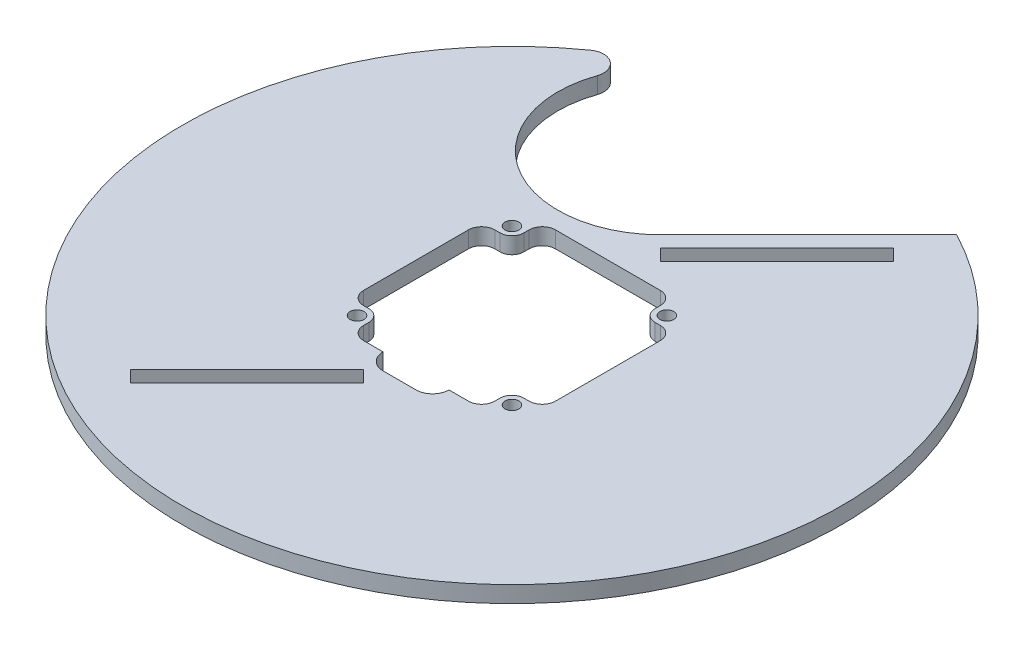
SolidWorks part; units mm, degrees
ref_plane "前基準面" through (0, 0, 0) normal (0, 0, 1) x (1, 0, 0)
ref_plane "上基準面" through (0, 0, 0) normal (0, 1, 0) x (1, 0, 0)
ref_plane "右基準面" through (0, 0, 0) normal (1, 0, 0) x (0, 0, -1)
sketch "草圖1" plane through (0, 0, 0) normal (0, 1, 0) x (1, 0, 0)
  line L2 (-99.6974, -7.7735) -> (17.2836, 109.2075) construction
  line L3 (8.3612, 36.6455) -> (43.7166, 72.0009)
  line L4 (-28.5, 28.5) -> (28.5, 28.5) construction
  line L5 (-28.5, 28.5) -> (-28.5, -28.5) construction
  line L6 (-28.5, -28.5) -> (28.5, -28.5) construction
  line L7 (28.5, 28.5) -> (28.5, -28.5) construction
  line L8 (8.3612, 36.6455) -> (4.8257, 40.181)
  line L9 (-18.8989, 23.5) -> (-18.8989, 25.1) construction
  line L10 (-25.1, 18.8989) -> (-23.5, 18.8989) construction
  line L11 (-18.8989, 23.5) -> (-18.8989, 25.1) construction
  line L12 (-25.1, 18.8989) -> (-23.5, 18.8989) construction
  line L13 (23.5, 18.8989) -> (25.1, 18.8989) construction
  line L14 (18.8989, 25.1) -> (18.8989, 23.5) construction
  line L15 (18.8989, -23.5) -> (18.8989, -25.1) construction
  line L16 (25.1, -18.8989) -> (23.5, -18.8989) construction
  line L17 (-23.5, -18.8989) -> (-25.1, -18.8989) construction
  line L18 (-18.8989, -25.1) -> (-18.8989, -23.5) construction
  line L19 (-15.8989, 28.1) -> (15.8989, 28.1) construction
  line L20 (28.1, 15.8989) -> (28.1, -15.8989) construction
  line L21 (-15.8989, -28.1) -> (15.8989, -28.1) construction
  line L22 (-28.1, 15.8989) -> (-28.1, -15.8989) construction
  line L23 (-19.8989, 23.5) -> (-19.8989, 25.1)
  line L24 (-15.8989, 29.1) -> (15.8989, 29.1)
  line L25 (19.8989, 25.1) -> (19.8989, 23.5)
  line L26 (23.5, 19.8989) -> (25.1, 19.8989)
  line L27 (29.1, 15.8989) -> (29.1, -15.8989)
  line L28 (25.1, -19.8989) -> (23.5, -19.8989)
  line L29 (19.8989, -23.5) -> (19.8989, -25.1)
  line L30 (-15.8989, -29.1) -> (15.8989, -29.1)
  line L31 (-19.8989, -25.1) -> (-19.8989, -23.5)
  line L32 (-23.5, -19.8989) -> (-25.1, -19.8989)
  line L33 (-29.1, 15.8989) -> (-29.1, -15.8989)
  line L34 (-25.1, 19.8989) -> (-23.5, 19.8989)
  line L35 (43.7166, 72.0009) -> (40.181, 75.5364)
  line L36 (40.181, 75.5364) -> (4.8257, 40.181)
  line L37 (40.181, 75.5364) -> (50.7877, 86.143) construction
  line L38 (-43.7166, -72.0009) -> (-40.181, -75.5364)
  line L39 (1.2902, 43.7166) -> (46.2405, 88.6669)
  line L40 (-8.3612, -36.6455) -> (-43.7166, -72.0009)
  line L41 (-40.181, -75.5364) -> (-4.8257, -40.181)
  line L42 (-8.3612, -36.6455) -> (-4.8257, -40.181)
  arc A20 (-57.6766, 81.6909) -> (46.2405, 88.6669) centre (0, 0) ccw
  circle A24 centre (0, 0) radius 20
  arc A27 (-15.8989, 28.1) -> (-18.8989, 25.1) centre (-15.8989, 25.1) ccw construction
  arc A28 (-25.1, 18.8989) -> (-28.1, 15.8989) centre (-25.1, 15.8989) ccw construction
  arc A29 (-23.5, 18.8989) -> (-18.8989, 23.5) centre (-23.5, 23.5) ccw construction
  arc A30 (-15.8989, 28.1) -> (-18.8989, 25.1) centre (-15.8989, 25.1) ccw construction
  arc A31 (-25.1, 18.8989) -> (-28.1, 15.8989) centre (-25.1, 15.8989) ccw construction
  arc A32 (-23.5, 18.8989) -> (-18.8989, 23.5) centre (-23.5, 23.5) ccw construction
  arc A33 (28.1, 15.8989) -> (25.1, 18.8989) centre (25.1, 15.8989) ccw construction
  arc A34 (18.8989, 25.1) -> (15.8989, 28.1) centre (15.8989, 25.1) ccw construction
  arc A35 (18.8989, 23.5) -> (23.5, 18.8989) centre (23.5, 23.5) ccw construction
  arc A36 (15.8989, -28.1) -> (18.8989, -25.1) centre (15.8989, -25.1) ccw construction
  arc A37 (25.1, -18.8989) -> (28.1, -15.8989) centre (25.1, -15.8989) ccw construction
  arc A38 (23.5, -18.8989) -> (18.8989, -23.5) centre (23.5, -23.5) ccw construction
  arc A39 (-28.1, -15.8989) -> (-25.1, -18.8989) centre (-25.1, -15.8989) ccw construction
  arc A40 (-18.8989, -25.1) -> (-15.8989, -28.1) centre (-15.8989, -25.1) ccw construction
  arc A41 (-18.8989, -23.5) -> (-23.5, -18.8989) centre (-23.5, -23.5) ccw construction
  arc A42 (-23.5, 19.8989) -> (-19.8989, 23.5) centre (-23.5, 23.5) ccw
  arc A43 (-15.8989, 29.1) -> (-19.8989, 25.1) centre (-15.8989, 25.1) ccw
  arc A44 (19.8989, 25.1) -> (15.8989, 29.1) centre (15.8989, 25.1) ccw
  arc A45 (19.8989, 23.5) -> (23.5, 19.8989) centre (23.5, 23.5) ccw
  arc A46 (29.1, 15.8989) -> (25.1, 19.8989) centre (25.1, 15.8989) ccw
  arc A47 (25.1, -19.8989) -> (29.1, -15.8989) centre (25.1, -15.8989) ccw
  arc A48 (23.5, -19.8989) -> (19.8989, -23.5) centre (23.5, -23.5) ccw
  arc A49 (15.8989, -29.1) -> (19.8989, -25.1) centre (15.8989, -25.1) ccw
  arc A50 (-19.8989, -25.1) -> (-15.8989, -29.1) centre (-15.8989, -25.1) ccw
  arc A51 (-19.8989, -23.5) -> (-23.5, -19.8989) centre (-23.5, -23.5) ccw
  arc A52 (-29.1, -15.8989) -> (-25.1, -19.8989) centre (-25.1, -15.8989) ccw
  arc A53 (-25.1, 19.8989) -> (-29.1, 15.8989) centre (-25.1, 15.8989) ccw
  circle A54 centre (0, 0) radius 65 construction
  circle A55 centre (-60.6477, -23.3851) radius 35 construction
  circle A56 centre (83.3354, 168.1883) radius 35 construction
  arc A58 (-50.072, 75.959) -> (1.2902, 43.7166) centre (-20.7041, 65.7109) ccw
  arc A59 (-57.6766, 81.6909) -> (-50.072, 75.959) centre (-54.7928, 77.6064) cw
  point P16 (0, 28.5)
  point P18 (-28.5, 0)
  point P96 (-60.6477, -23.5)
  dimension "D1" = 4
  dimension "D2" = 200
  dimension "D3" = 130
  dimension "D4" = 40
  dimension "D6" = 1
  dimension "D8" = 45
  dimension "D11" = 15
  dimension "D12" = 70
  dimension "D13" = 5
  dimension "D15" = 2
  dimension "D5" = 57
  dimension "D9" = 5
  dimension "D10" = 50
  dimension "D7" = 45
  dimension "D14" = 5
extrude "填料-伸長1" add sketch "草圖1" against normal blind 5 contours A20 A53 L34 A42 L23 A43 L24 A44 L25 A45 L26 A46 L27 A47 L28 A48 L29 A49 L30 A50 L31 A51 L32 A52 L33 region at (25.7095, 0, -64.2476)
sketch "草圖2" plane through (0, 0, 0) normal (0, 1, 0) x (1, 0, 0)
  line L1 (-23.5, 23.5) -> (23.5, 23.5)
  line L2 (-23.5, 23.5) -> (-23.5, -23.5)
  line L3 (-23.5, -23.5) -> (23.5, -23.5)
  line L4 (23.5, 23.5) -> (23.5, -23.5)
  point P9 (23.5, 0)
  point P15 (0, 23.5)
  dimension "D1" = 47
sketch "草圖5" plane through (0, 0, 0) normal (0, 1, 0) x (1, 0, 0)
  line L0 (-5, -29.1) -> (5, -29.1) construction
  line L1 (-15.8989, -29.1) -> (15.8989, -29.1) construction
  line L2 (-5, -24.1) -> (5, -24.1)
  line L3 (-5, -34.1) -> (5, -34.1)
  arc A0 (-5, -24.1) -> (-5, -34.1) centre (-5, -29.1) ccw
  arc A1 (5, -34.1) -> (5, -24.1) centre (5, -29.1) ccw
  point P4 (0, -29.1)
  dimension "D1" = 10
  dimension "D2" = 10
extrude "除料-伸長1" cut sketch "草圖5" against normal through all both and the other way through all contours L2 A1 L3 A0
hole_wizard "M5 螺紋孔1" positions "草圖3" profile "草圖4" tap size "M5" standard "ISO" end condition through all
sketch "草圖3" plane through (0, 0, 0) normal (0, 1, 0) x (1, 0, 0)
  point P13 (23.5, 23.5)
  point P16 (23.5, -23.5)
  point P19 (-23.5, -23.5)
  point P22 (-23.5, 23.5)
sketch "草圖4" plane through (23.5, 0, -23.5) normal (1, 0, 0) x (0, 0, 1)
  line L0 (0, 0) -> (0, 5)
  line L1 (0, 5) -> (2.1, 5)
  line L2 (2.1, 5) -> (2.1, 0)
  line L5 (2.1, 0) -> (0, 0)
  line L11 (0, -6.35) -> (0, 107.95) construction
  dimension "貫穿螺孔鑽直徑" = 4.2
  dimension "貫穿螺孔鑽深度" = 5
cosmetic thread "鑽孔螺紋1" parameters "D2"=5
cosmetic thread "鑽孔螺紋2" parameters "D2"=5
cosmetic thread "鑽孔螺紋3" parameters "D2"=5
cosmetic thread "鑽孔螺紋4" parameters "D2"=5
